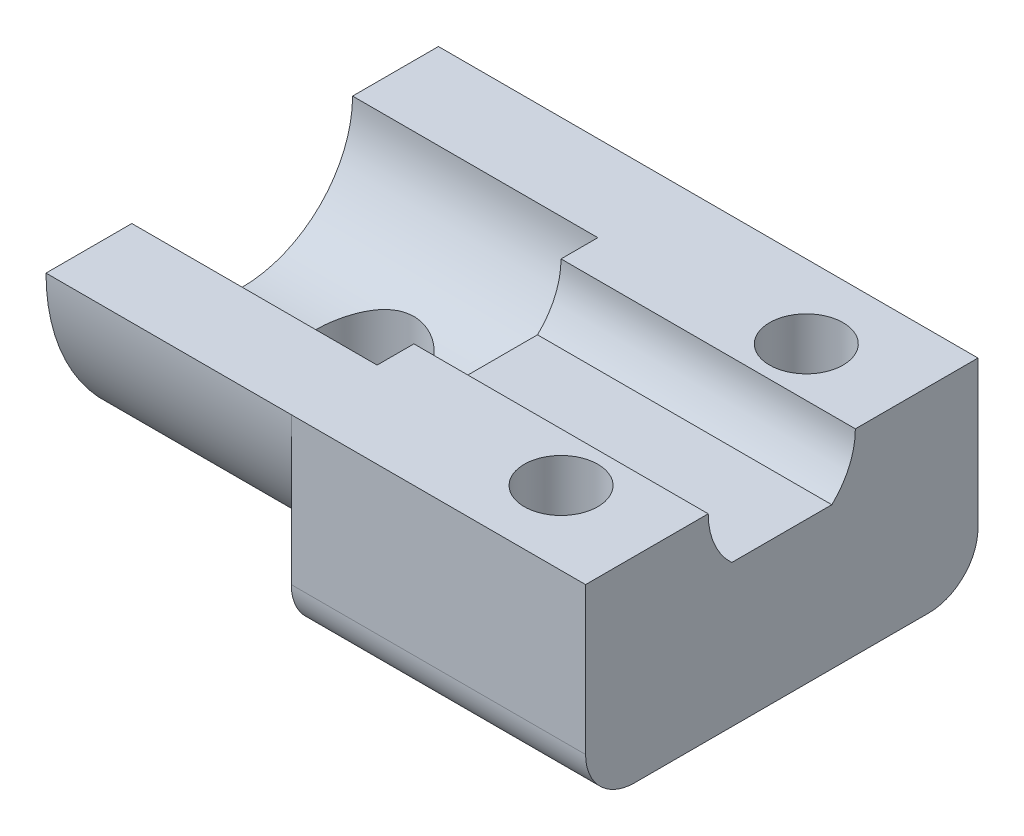
SolidWorks part; units mm, degrees
material "6061 合金"
ref_plane "前视基准面" through (0, 0, 0) normal (0, 0, 1) x (1, 0, 0)
ref_plane "上视基准面" through (0, 0, 0) normal (0, 1, 0) x (1, 0, 0)
ref_plane "右视基准面" through (0, 0, 0) normal (1, 0, 0) x (0, 0, -1)
sketch "草图1" plane through (0, 0, 0) normal (0, 1, 0) x (1, 0, 0)
  line L0 (-9.1923, 0) -> (20.415, 0) construction
  line L1 (-6, 8) -> (6, 8)
  line L2 (-6, 8) -> (-6, -8)
  line L3 (-6, -8) -> (6, -8)
  line L4 (6, 8) -> (6, -8)
  line L5 (-6, 8) -> (6, -8) construction
  line L6 (-6, -8) -> (6, 8) construction
  line L7 (0, 17.8948) -> (0, -16.2359) construction
  circle A0 centre (2, 5) radius 1.5
  circle A1 centre (2, -5) radius 1.5
  point P0 (0, 0)
  dimension "D3" = 3
  dimension "D1" = 12
  dimension "D2" = 16
  dimension "D4" = 3
  dimension "D5" = 4
extrude "凸台-拉伸1" add sketch "草图1" along normal blind 8
sketch "草图2" plane through (6, 0, 0) normal (1, 0, 0) x (0, 0, -1)
  line L0 (-8, 8) -> (8, 8) construction
  line L1 (-2.0396, 5.8) -> (2.0396, 5.8)
  arc A0 (2.0396, 5.8) -> (-2.0396, 5.8) centre (0, 8) ccw
  dimension "D1" = 6
  dimension "D2" = 2.2
extrude "切除-拉伸1" cut sketch "草图2" against normal blind 25
sketch "草图3" plane through (-6, 0, 0) normal (-1, 0, 0) x (0, 0, 1)
  line L0 (-8, 8) -> (8, 8) construction
  line L1 (-8, 8) -> (-4.5, 8)
  line L2 (4.5, 8) -> (8, 8)
  arc A0 (-8, 8) -> (8, 8) centre (0, 8) ccw
  arc A1 (-4.5, 8) -> (4.5, 8) centre (0, 8) ccw
  dimension "D1" = 16
  dimension "D2" = 9
extrude "凸台-拉伸2" add sketch "草图3" along normal blind 10
fillet "圆角1" radius 2 2 edges at (0, 0, 8) (0, 0, -8)
sketch "草图4" plane through (0, 8, 0) normal (0, 1, 0) x (1, 0, 0)
  line L0 (-16, 4.5) -> (-16, -4.5) construction
  circle A0 centre (-11, 0) radius 2
  dimension "D1" = 4
  dimension "D2" = 5
extrude "切除-拉伸2" cut sketch "草图4" against normal blind 20
